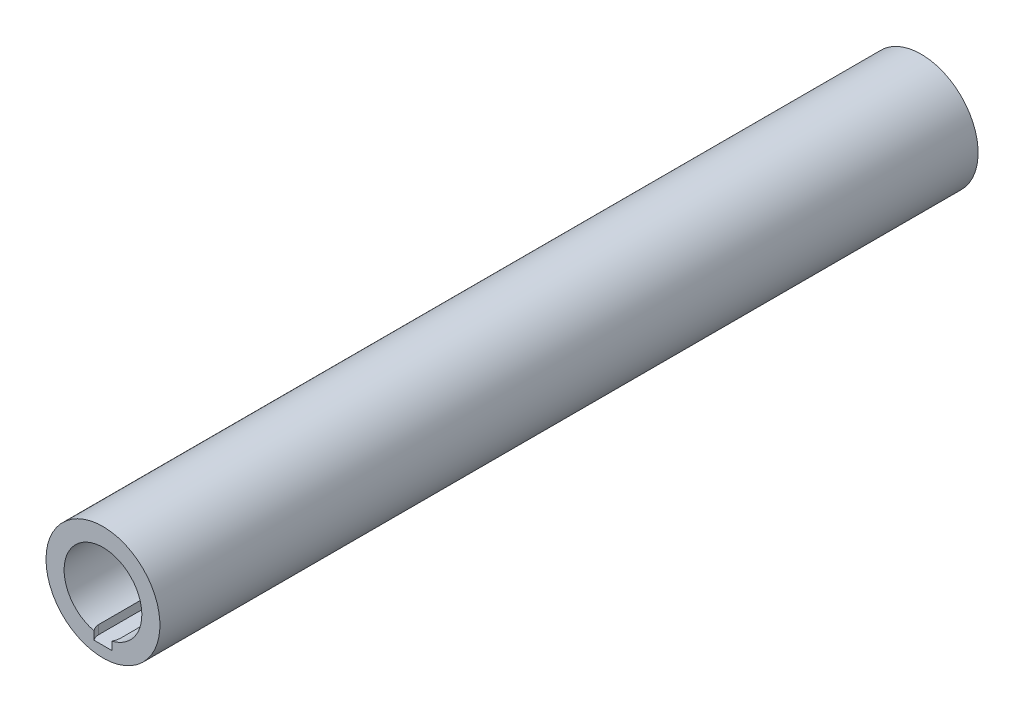
SolidWorks part; units mm, degrees
ref_plane "Front Plane" through (0, 0, 0) normal (0, 0, 1) x (1, 0, 0)
ref_plane "Top Plane" through (0, 0, 0) normal (0, 1, 0) x (1, 0, 0)
ref_plane "Right Plane" through (0, 0, 0) normal (1, 0, 0) x (0, 0, -1)
ref_plane "Plane1" through (0, 0, 0) normal (0, -1, 0) x (1, 0, 0)
sketch "Sketch1" plane through (0, 0, 0) normal (0, -1, 0) x (1, 0, 0)
  line L0 (38.2, -516.5186) -> (38.2, 58)
  line L1 (38.2, 58) -> (25.5, 58)
  line L2 (25.5, 58) -> (25.5, -12)
  line L3 (25.5, -12) -> (29, -12)
  line L4 (29, -12) -> (29, -22)
  line L5 (29, -22) -> (20.2, -22)
  line L6 (20.2, -22) -> (20.2, -436.5186)
  line L7 (20.2, -436.5186) -> (29, -436.5186)
  line L8 (29, -436.5186) -> (29, -446.5186)
  line L9 (29, -446.5186) -> (25.5, -446.5186)
  line L10 (25.5, -446.5186) -> (25.5, -516.5186)
  line L11 (25.5, -516.5186) -> (38.2, -516.5186)
  line L12 (-1.8, 70) -> (-1.8, -504.5186) construction
  dimension "D1" = 44
  dimension "D2" = 3.5
  dimension "D3" = 54.6
  dimension "D4" = 80
  dimension "D5" = 70
  dimension "D6" = 10
  dimension "D7" = 414.5186
  dimension "D8" = 10
  dimension "D9" = 70
revolve "Revolve1" add sketch "Sketch1" angle 360 about L12 reverse direction yes
ref_axis "Axis1" through (-1.8, 0, 302.5128) along (0, 0, -1)
ref_plane "Plane2" through (0, -27.3, 0) normal (0, 1, 0) x (1, 0, 0)
sketch "Sketch3" plane through (0, -27.3, 0) normal (0, 1, 0) x (1, 0, 0)
  line L0 (-1.8, 521.5186) -> (-1.8, 461.5186) construction
  line L1 (-1.8, -302.5128) -> (-1.8, 827.3528) construction
  line L2 (6.2, 521.5186) -> (6.2, 461.5186)
  line L3 (-9.8, 521.5186) -> (-9.8, 461.5186)
  line L4 (-1.8, -53) -> (-1.8, 7) construction
  line L5 (-9.8, -53) -> (-9.8, 7)
  line L6 (6.2, -53) -> (6.2, 7)
  arc A0 (6.2, 521.5186) -> (-9.8, 521.5186) centre (-1.8, 521.5186) ccw
  arc A1 (-9.8, 461.5186) -> (6.2, 461.5186) centre (-1.8, 461.5186) ccw
  arc A2 (-9.8, -53) -> (6.2, -53) centre (-1.8, -53) ccw
  arc A3 (6.2, 7) -> (-9.8, 7) centre (-1.8, 7) ccw
  point P4 (-1.8, 491.5186)
  point P9 (-1.8, -23)
  dimension "D1" = 8
  dimension "D4" = 8
  dimension "D2" = 454.5186
  dimension "D5" = 60
  dimension "D6" = 60
extrude "Cut-Extrude1" cut sketch "Sketch3" against normal blind 5 and the other way blind 10
